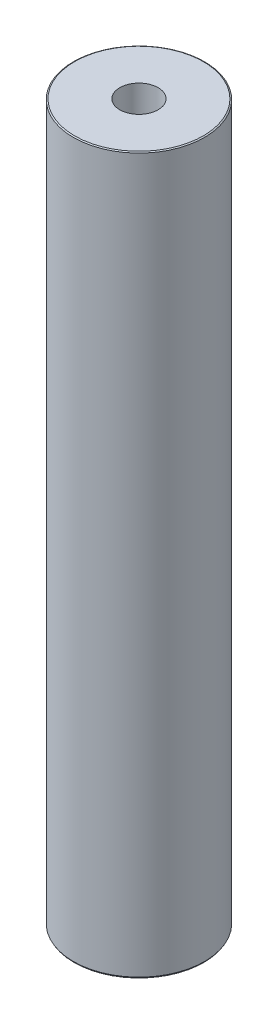
SolidWorks part; units mm, degrees
ref_plane "Front Plane" through (0, 0, 0) normal (0, 0, 1) x (1, 0, 0)
ref_plane "Top Plane" through (0, 0, 0) normal (0, 1, 0) x (1, 0, 0)
ref_plane "Right Plane" through (0, 0, 0) normal (1, 0, 0) x (0, 0, -1)
sketch "Sketch1" plane through (0, 0, 0) normal (0, 1, 0) x (1, 0, 0)
  circle A0 centre (0, 0) radius 55
  dimension "SHAFT_OD" = 110
extrude "Boss-Extrude1" add sketch "Sketch1" along normal blind 600
sketch "Sketch2" plane through (0, 0, 0) normal (0, 1, 0) x (1, 0, 0)
  circle A0 centre (0, 0) radius 16.0922
  dimension "BORE_D" = 32.1843
extrude "Cut-Extrude1" cut sketch "Sketch2" along normal through all
chamfer "Chamfer1" distance 0.6059 angle 60 2 edges at (0, 600, 55) (0, 0, 55) first distance on face at (0, 600, 55) first distance on face at (0, 0, 16.0922)
